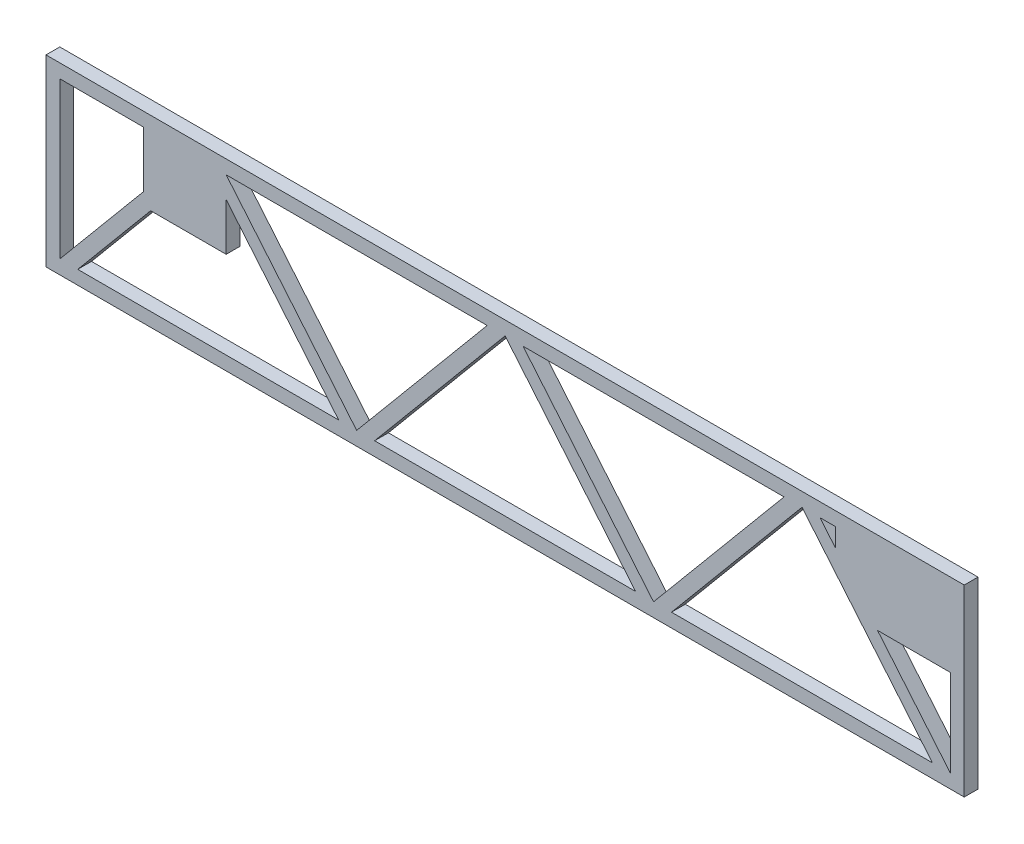
SolidWorks part; units mm, degrees
material "轻木"
ref_plane "前视基准面" through (0, 0, 0) normal (0, 0, 1) x (1, 0, 0)
ref_plane "上视基准面" through (0, 0, 0) normal (0, 1, 0) x (1, 0, 0)
ref_plane "右视基准面" through (0, 0, 0) normal (1, 0, 0) x (0, 0, -1)
other "Configuration Table"
sketch "草图1" plane through (0, 0, 0) normal (0, 0, 1) x (1, 0, 0)
  line L1 (-100, 20) -> (100, 20)
  line L2 (-100, 20) -> (-100, -20)
  line L3 (-100, -20) -> (100, -20)
  line L4 (100, 20) -> (100, -20)
  line L5 (-100, 20) -> (100, -20) construction
  line L6 (-100, -20) -> (100, 20) construction
  line L10 (-97, -17) -> (-68.5769, 17)
  line L11 (-93.0898, -17) -> (-64.6667, 17)
  line L12 (-60.7565, 17) -> (-32.3333, -17)
  line L13 (-64.6667, 17) -> (-36.2435, -17)
  line L14 (-28.4231, -17) -> (0, 17)
  line L15 (-32.3333, -17) -> (-3.9102, 17)
  line L16 (0, 0) -> (0, -16) construction
  line L17 (28.4231, -17) -> (0, 17)
  line L18 (32.3333, -17) -> (3.9102, 17)
  line L19 (60.7565, 17) -> (32.3333, -17)
  line L20 (64.6667, 17) -> (36.2435, -17)
  line L21 (93.0898, -17) -> (64.6667, 17)
  line L22 (97, -17) -> (68.5769, 17)
  line L28 (97, 17) -> (72, 17)
  line L29 (97, 17) -> (97, 2)
  line L34 (-97, 17) -> (-97, -17)
  line L35 (-97, -17) -> (97, -17)
  line L36 (97, 17) -> (97, -17)
  line L37 (-97, 17) -> (97, 17)
  line L38 (97, 2) -> (72, 2)
  line L39 (72, 17) -> (72, 2)
  line L44 (-78.7565, 17) -> (-60.7565, 17)
  line L45 (-78.7565, 17) -> (-78.7565, 2)
  line L50 (-78.7565, 2) -> (-60.7565, 2)
  line L51 (-60.7565, 17) -> (-60.7565, 2)
  point P0 (0, 0)
  dimension "D1" = 40
  dimension "D2" = 200
  dimension "D4" = 3
  dimension "D5" = 3
  dimension "D6" = 25
  dimension "D7" = 15
  dimension "D8" = 15
  dimension "D9" = 18
  dimension "D3" = 3
  dimension "D10" = 3
extrude "凸台-拉伸1" add sketch "草图1" along normal blind 3 contours L4 L1 L2 L3 L34 L37 L28 L29 L36 L35 | L22 L38 L21 L35 | L28 L39 L22 L38 L29 | L22 L39 L21 L38 | L39 L22 L37 L21 | L37 L19 L35 L20 | L37 L17 L35 L18 | L37 L15 L35 L14 | L12 L51 L13 L35 | L50 L45 L10 L35 L11 | L51 L13 L11 L50 | L45 L50 L11 L37 L10 | L37 L45 L10 | L51 L37 L13 region at (0, 17.9604, 0) region at (-86.7787, -7.0519, 0) region at (-75.3633, 12.941, 0) region at (-72.491, 9.895, 0) region at (-66.7723, 7.4837, 0) region at (-47.4984, -1.1406, 0) region at (-62.0599, 15.4409, 0) region at (-16.1667, 0, 0) region at (16.1667, 0, 0) region at (48.5, 0, 0) region at (69.1924, 13.6416, 0) region at (87.1031, -7.5, 0) region at (75.6697, 6.3897, 0) region at (85.9458, 10.0906, 0)
